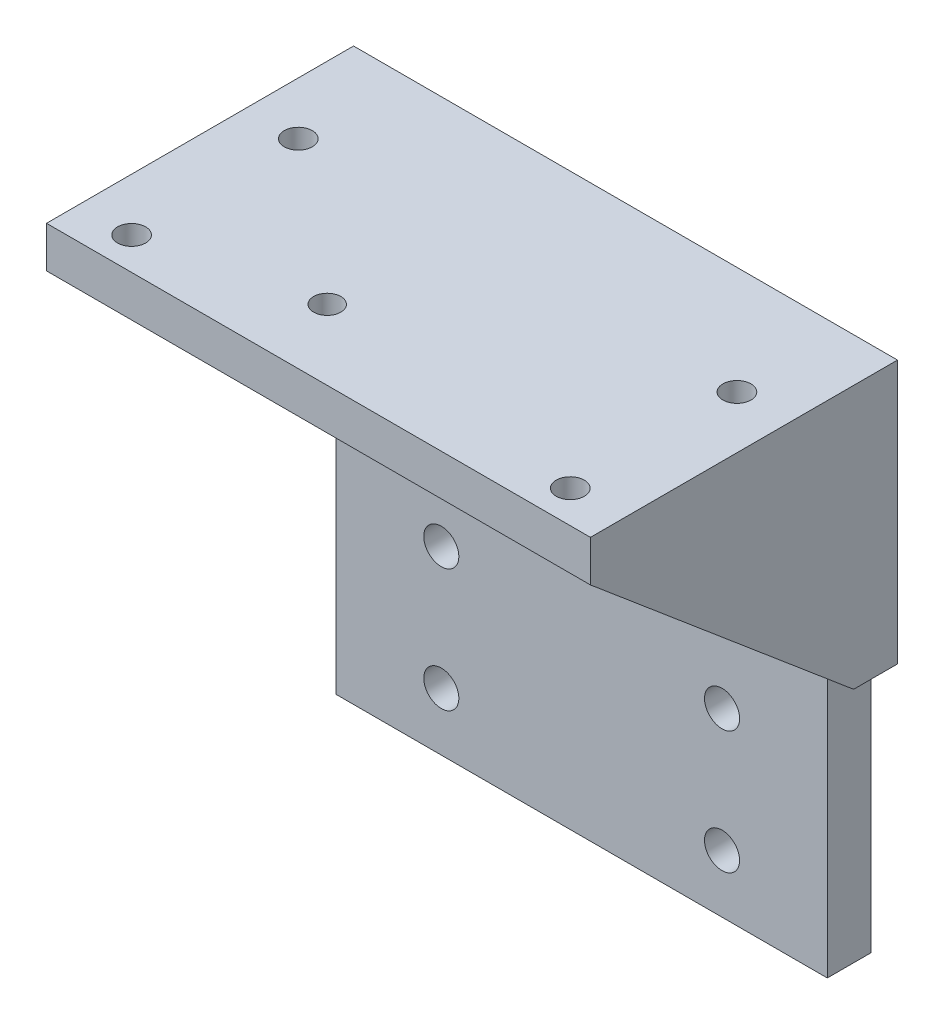
SolidWorks part; units mm, degrees
ref_plane "前视基准面" through (0, 0, 0) normal (0, 0, 1) x (1, 0, 0)
ref_plane "上视基准面" through (0, 0, 0) normal (0, 1, 0) x (1, 0, 0)
ref_plane "右视基准面" through (0, 0, 0) normal (1, 0, 0) x (0, 0, -1)
other "Configuration Table"
sketch "草图1" plane through (0, 0, 0) normal (0, 0, 1) x (1, 0, 0)
  line L1 (-28, -30) -> (28, -30)
  line L2 (-28, -30) -> (-28, 30)
  line L3 (-28, 30) -> (28, 30)
  line L4 (28, -30) -> (28, 30)
  line L5 (-28, -30) -> (28, 30) construction
  line L6 (-28, 30) -> (28, -30) construction
  point P0 (0, 0)
  dimension "D1" = 56
  dimension "D2" = 60
extrude "凸台-拉伸1" add sketch "草图1" along normal blind 5
sketch "草图2" plane through (0, 0, 5) normal (0, 0, 1) x (1, 0, 0)
  line L0 (-16, -23.4) -> (-16, -9.4) construction
  line L1 (-28, -30) -> (28, -30) construction
  line L2 (-28, 30) -> (-28, -30) construction
  circle A0 centre (-16, -23.4) radius 2
  circle A1 centre (-16, -9.4) radius 2
  dimension "D3" = 4
  dimension "D1" = 14
  dimension "D2" = 6.6
  dimension "D4" = 12
extrude "切除-拉伸1" cut sketch "草图2" against normal blind 5
mirror "镜向1" about plane through (0, 0, 0) normal (1, 0, 0) of "切除-拉伸1"
sketch "草图3" plane through (0, 0, 5) normal (0, 0, 1) x (1, 0, 0)
  line L0 (28, -30) -> (28, 30) construction
  line L1 (-28, 30) -> (28, 30)
  line L2 (-28, 30) -> (-28, 25.3)
  line L3 (-28, 25.3) -> (28, 25.3)
  line L4 (28, 30) -> (28, 25.3)
  dimension "D1" = 4.7
extrude "凸台-拉伸2" add sketch "草图3" along normal blind 30
sketch "草图4" plane through (0, 30, 0) normal (0, 1, 0) x (1, 0, 0)
  line L0 (28, 0) -> (-28, 0) construction
  line L1 (-28, -35) -> (-28, 0) construction
  circle A0 centre (-7, -27) radius 1.55
  dimension "D3" = 3.1
  dimension "D1" = 27
  dimension "D2" = 21
extrude "切除-拉伸2" cut sketch "草图4" against normal blind 40
sketch "草图5" plane through (0, 0, 5) normal (0, 0, 1) x (1, 0, 0)
  line L1 (-28, 25.3) -> (-3, 25.3)
  line L2 (-28, 25.3) -> (-28, 1.3)
  line L3 (-28, 1.3) -> (-3, 1.3)
  line L4 (-3, 25.3) -> (-3, 1.3)
  dimension "D1" = 24
  dimension "D2" = 25
extrude "凸台-拉伸3" add sketch "草图5" along normal blind 4.3
sketch "草图6" plane through (-28, 0, 0) normal (-1, 0, 0) x (0, 0, 1)
  line L0 (0, 30) -> (0, 0)
  line L1 (0, 30) -> (0, -30) construction
  line L3 (35, 25.3) -> (35, 30)
  line L4 (35, 30) -> (0, 30)
  line L5 (0, 0) -> (5, 0)
  line L6 (5, 1.3) -> (5, -30) construction
  line L7 (5, 0) -> (35, 25.3)
  dimension "D1" = 30
extrude "凸台-拉伸4" add sketch "草图6" along normal blind 3
mirror "镜向2" about plane through (0, 0, 0) normal (1, 0, 0) of "凸台-拉伸4"
sketch "草图8" plane through (0, 25.3, 0) normal (0, -1, 0) x (1, 0, 0)
  line L0 (-28, 9.3) -> (-28, 35) construction
  line L1 (-25, 12.3) -> (25, 12.3) construction
  line L2 (-25, 12.3) -> (-25, 31.3) construction
  line L3 (-25, 31.3) -> (25, 31.3) construction
  line L4 (25, 12.3) -> (25, 31.3) construction
  line L5 (-25, 12.3) -> (25, 31.3) construction
  line L6 (-25, 31.3) -> (25, 12.3) construction
  line L7 (-28, 9.3) -> (-3, 9.3) construction
  line L8 (-28, 35) -> (28, 35) construction
  circle A0 centre (-25, 31.3) radius 1.6
  circle A1 centre (25, 31.3) radius 1.6
  circle A2 centre (25, 12.3) radius 1.6
  circle A3 centre (-25, 12.3) radius 1.6
  point P0 (0, 21.8)
  dimension "D5" = 3.2
  dimension "D1" = 3
  dimension "D2" = 3
  dimension "D3" = 21.8
  dimension "D4" = 3.7
extrude "切除-拉伸3" cut sketch "草图8" against normal blind 5
